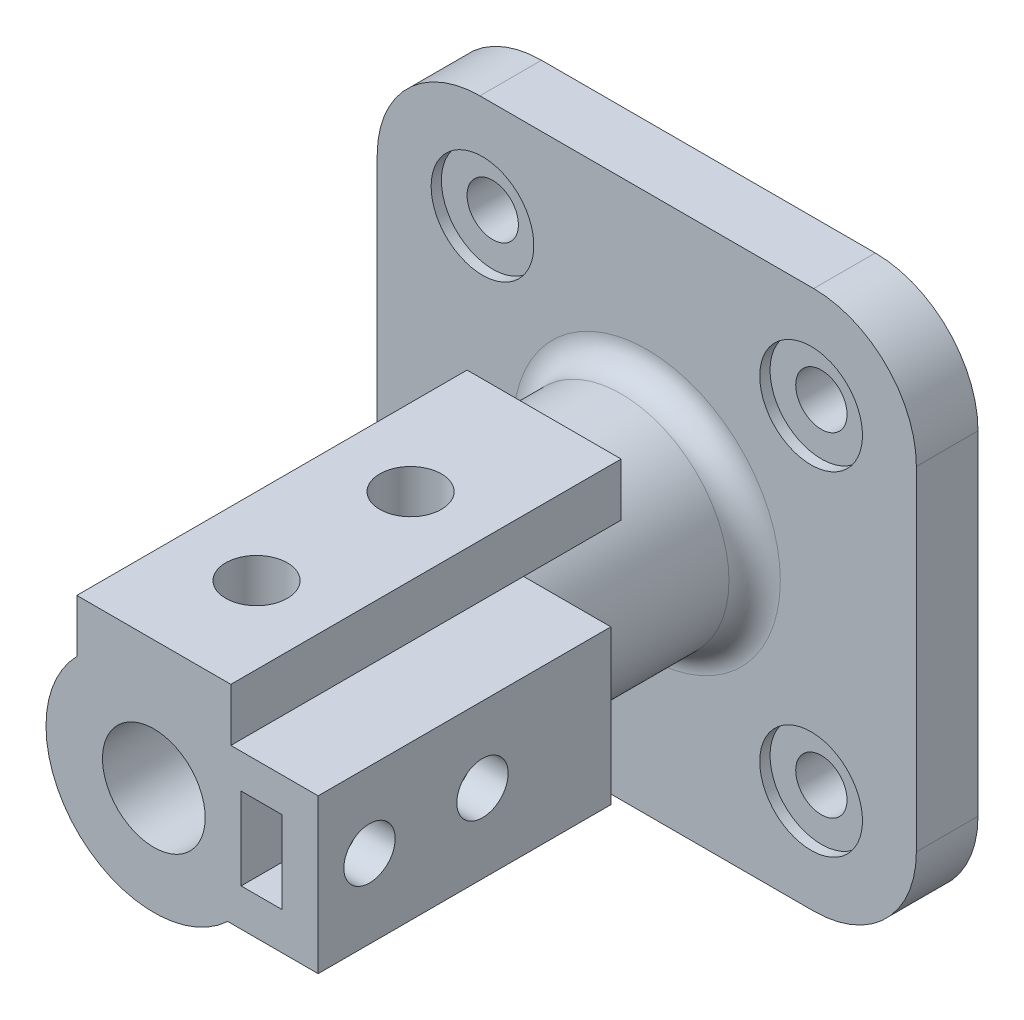
SolidWorks part; units mm, degrees
ref_plane "Front Plane" through (0, 0, 0) normal (0, 0, 1) x (1, 0, 0)
ref_plane "Top Plane" through (0, 0, 0) normal (0, 1, 0) x (1, 0, 0)
ref_plane "Right Plane" through (0, 0, 0) normal (1, 0, 0) x (0, 0, -1)
sketch "Sketch1" plane through (0, 0, 0) normal (0, 0, 1) x (1, 0, 0)
  circle A0 centre (0, 0) radius 21
  dimension "D1" = 42
extrude "Boss-Extrude1" add sketch "Sketch1" along normal mid plane 96
sketch "Sketch2" plane through (0, 0, -48) normal (0, 0, -1) x (-1, 0, 0)
  line L0 (-92.3222, 0) -> (93.2536, 0) construction
  line L1 (-32.5, 52.5) -> (32.5, 52.5)
  line L2 (-52.5, 32.5) -> (-52.5, -32.5)
  line L3 (-32.5, -52.5) -> (32.5, -52.5)
  line L4 (52.5, 32.5) -> (52.5, -32.5)
  line L5 (-52.5, 52.5) -> (52.5, -52.5) construction
  line L6 (-52.5, -52.5) -> (52.5, 52.5) construction
  line L7 (0, 59.3929) -> (0, -60.3035)
  arc A0 (32.5, 52.5) -> (52.5, 32.5) centre (32.5, 32.5) cw
  arc A1 (52.5, -32.5) -> (32.5, -52.5) centre (32.5, -32.5) cw
  arc A2 (-32.5, -52.5) -> (-52.5, -32.5) centre (-32.5, -32.5) cw
  arc A3 (-52.5, 32.5) -> (-32.5, 52.5) centre (-32.5, 32.5) cw
  circle A4 centre (-32, 32.5) radius 10
  circle A5 centre (-32, 32.5) radius 5
  circle A6 centre (-32, -32.5) radius 10
  circle A7 centre (-32, -32.5) radius 5
  circle A8 centre (32, 32.5) radius 5
  circle A9 centre (32, -32.5) radius 5
  circle A10 centre (32, -32.5) radius 10
  circle A11 centre (32, 32.5) radius 10
  point P0 (0, 0)
  point P28 (0, 0)
  point P29 (0, 0)
  circle M5 centre (0, 0) radius 21
  dimension "D3" = 20
  dimension "D4" = 20
  dimension "D5" = 10
  dimension "D6" = 20
  dimension "D7" = 10
  dimension "D1" = 105
  dimension "D2" = 105
  dimension "D8" = 65
  dimension "D9" = 32.5
  dimension "D10" = 32
extrude "Boss-Extrude2" add sketch "Sketch2" along normal blind 12 contours A3 L2 A2 L3 L7 L1 A6 A4 M5 | A1 L4 A0 L1 L7 L3 A10 A11 M5 | A4 A5 | A6 A7 | A11 A8 | A10 A9 | L7 M5 | L7 M5 region at (27.4086, 0, -48) region at (-27.4086, 0, -48) region at (-8.9127, 0, -48) region at (8.9127, 0, -48) region at (41.7172, 32.5, -48) region at (41.7172, -32.5, -48) region at (-22.2828, -32.5, -48) region at (-22.2828, 32.5, -48)
extrude "Cut-Extrude1" cut sketch "Sketch2<3>" along normal blind 2 contours A11 A8 | A4 A5 | A6 A7 | A10 A9 region at (41.7172, 32.5, -48) region at (41.7172, -32.5, -48) region at (-22.2828, -32.5, -48) region at (-22.2828, 32.5, -48)
sketch "Sketch2<3>" plane through (0, 0, -48) normal (0, 0, -1) x (-1, 0, 0) same geometry as "Sketch2"
fillet "Fillet8" radius 5 1 edges at (-21, 0, -48)
sketch "Sketch3" plane through (0, 0, 48) normal (0, 0, 1) x (1, 0, 0)
  line L0 (-15, 25) -> (15, 25)
  line L1 (15, 25) -> (15, 14.6969)
  line L2 (-15, 25) -> (-15, 14.6969)
  circle A0 centre (0, 0) radius 21 construction
  arc A1 (15, 14.6969) -> (-15, 14.6969) centre (0, 0) ccw
  point P8 (0, 0)
  point P9 (0, 0)
  dimension "D1" = 25
  dimension "D2" = 30
  dimension "D3" = 15
extrude "Boss-Extrude3" add sketch "Sketch3" against normal blind 76 contours L0 L1 A1 L2
sketch "Sketch4" plane through (0, 0, 48) normal (0, 0, 1) x (1, 0, 0)
  line L0 (15, 14.6969) -> (32, 14.6969)
  line L1 (32, 14.6969) -> (32, -15.3031)
  line L2 (32, -15.3031) -> (14.3811, -15.3031)
  line L4 (17, 8) -> (25, 8)
  line L5 (17, 8) -> (17, -8)
  line L6 (17, -8) -> (25, -8)
  line L7 (25, 8) -> (25, -8)
  circle A0 centre (0, 0) radius 21 construction
  arc A1 (14.3811, -15.3031) -> (19.4165, -8) centre (0, 0) ccw
  arc A2 (19.4165, 8) -> (15, 14.6969) centre (0, 0) ccw
  arc M8 (-15, 14.6969) -> (15, 14.6969) centre (0, 0) ccw
  dimension "D5" = 16
  dimension "D1" = 32
  dimension "D2" = 30
  dimension "D3" = 8
  dimension "D4" = 17
  dimension "D6" = 8
extrude "Boss-Extrude4" add sketch "Sketch4" against normal blind 57 contours L4 L7 L6 L2 L1 L0 M8 | L7 L6 L5 L4 region at (26.002, -0.4972, 48)
extrude "Cut-Extrude2" cut sketch "Sketch4<3>" against normal blind 50 contours L5 L6 L4 M8 | L7 L4 L6 M8 region at (18.7718, 0, 48) region at (22.7158, 0, 48)
sketch "Sketch4<3>" plane through (0, 0, 48) normal (0, 0, 1) x (1, 0, 0) same geometry as "Sketch4"
sketch "Sketch5" plane through (0, 0, 48) normal (0, 0, 1) x (1, 0, 0)
  circle A0 centre (0, 0) radius 10
  dimension "D1" = 20
extrude "Cut-Extrude3" cut sketch "Sketch5" against normal through all
sketch "Sketch6" plane through (0, 25, 0) normal (0, 1, 0) x (1, 0, 0)
  line L0 (-15, -48) -> (15, -48) construction
  circle A0 centre (0, 2) radius 6
  circle A1 centre (0, -28) radius 6
  dimension "D3" = 12
  dimension "D4" = 12
  dimension "D1" = 30
  dimension "D2" = 20
extrude "Cut-Extrude4" cut sketch "Sketch6" against normal up to next
sketch "Sketch7" plane through (32, 0, 0) normal (1, 0, 0) x (0, 0, -1)
  line L0 (-48, 14.6969) -> (-48, -15.3031) construction
  circle A0 centre (-38, 0) radius 5
  circle A1 centre (-16, 0) radius 5
  point P6 (0, 0)
  point P7 (0, 0)
  dimension "D1" = 10
  dimension "D2" = 10
  dimension "D3" = 22
  dimension "D4" = 10
extrude "Cut-Extrude5" cut sketch "Sketch7" against normal up to next
